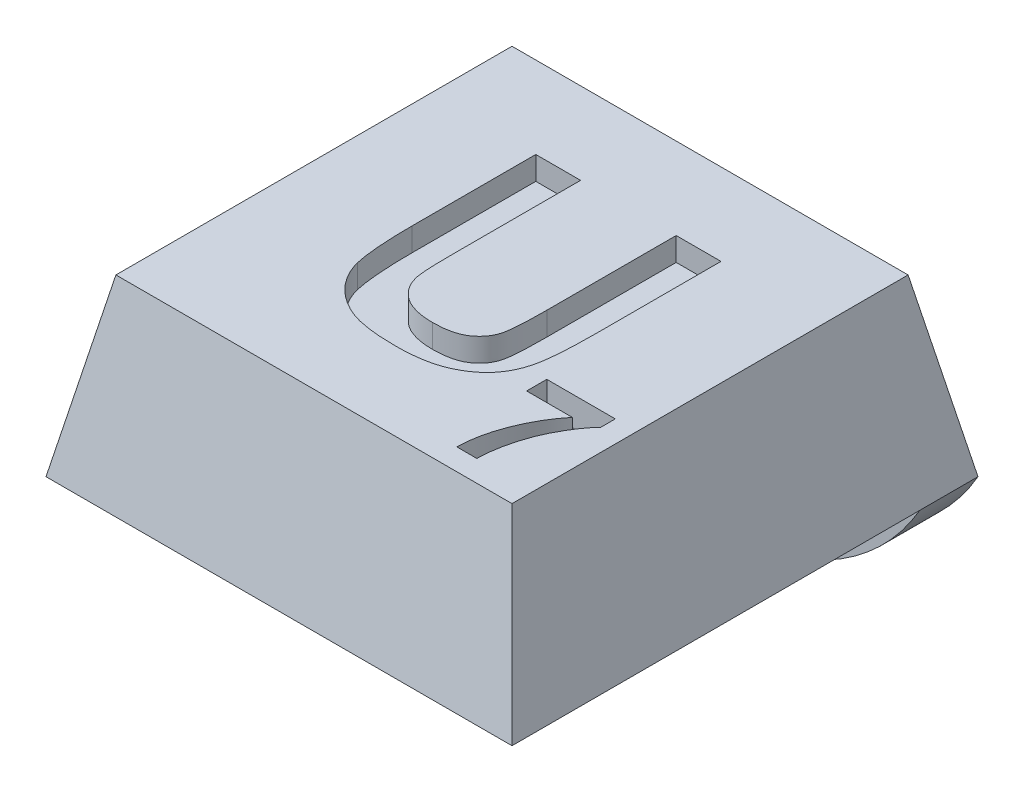
SolidWorks part; units mm, degrees
ref_plane "Front Plane" through (0, 0, 0) normal (0, 0, 1) x (1, 0, 0)
ref_plane "Top Plane" through (0, 0, 0) normal (0, 1, 0) x (1, 0, 0)
ref_plane "Right Plane" through (0, 0, 0) normal (1, 0, 0) x (0, 0, -1)
sketch "Sketch1" plane through (0, 0, 0) normal (0, 1, 0) x (1, 0, 0)
  line L1 (0, 0) -> (8, 0)
  line L2 (0, 0) -> (0, 8)
  line L3 (0, 8) -> (8, 8)
  line L4 (8, 0) -> (8, 8)
  dimension "D1" = 8
  dimension "D2" = 8
extrude "Boss-Extrude1" add sketch "Sketch1" along normal blind 3
sketch "Sketch2" plane through (0, 0, 0) normal (0, 0, 1) x (1, 0, 0)
  line L0 (0, 0) -> (0.6, 3)
  line L1 (0, 3) -> (8, 3) construction
  line L2 (0.6, 3) -> (0, 3)
  line L3 (0, 3) -> (0, 0)
  line L4 (8, 0) -> (7.4, 3)
  line L5 (7.4, 3) -> (8, 3)
  line L6 (8, 3) -> (8, 0)
  dimension "D1" = 0.6
  dimension "D2" = 0.6
extrude "Cut-Extrude1" cut sketch "Sketch2" against normal through all both and the other way through all
sketch "Sketch3" plane through (0, 0, 0) normal (1, 0, 0) x (0, 0, -1)
  line L0 (0, 0) -> (0.6, 3)
  line L1 (8, 3) -> (0, 3) construction
  line L2 (0.6, 3) -> (0, 3)
  line L3 (0, 3) -> (0, 0)
  line L4 (8, 3) -> (7.4, 3)
  line L5 (7.4, 3) -> (8, 0)
  line L6 (8, 3) -> (8, 0)
  dimension "D1" = 0.6
  dimension "D2" = 0.6
extrude "Cut-Extrude2" cut sketch "Sketch3" along normal blind 11
sketch "Sketch4" plane through (0, 0, 0) normal (0, -1, 0) x (1, 0, 0)
  line L0 (8, 0) -> (8, -8) construction
  line L3 (0, 0) -> (8, 0) construction
  circle A0 centre (4, -3.75) radius 1.75
  dimension "D1" = 3.5
  dimension "D2" = 4
  dimension "D3" = 3.75
extrude "Cut-Extrude3" cut sketch "Sketch4" against normal blind 0.4
sketch "Sketch5" plane through (0, 0, 0) normal (0, -1, 0) x (1, 0, 0)
  line L0 (8, 0) -> (8, -8) construction
  line L1 (0, -8) -> (8, -8)
  line L2 (0, -8) -> (0, -7)
  line L3 (0, -7) -> (8, -7)
  line L4 (8, -8) -> (8, -7)
  dimension "D1" = 1
extrude "Boss-Extrude2" add sketch "Sketch5" along normal blind 2
fillet "Fillet1" radius 4 2 edges at (8, -2, -7.5) (0, -2, -7.5)
sketch "Sketch6" plane through (0, 3, 0) normal (0, 1, 0) x (1, 0, 0)
  text T0 "U" font "Arial" height 4
extrude "Cut-Extrude4" cut sketch "Sketch6" against normal blind 0.4
sketch "Sketch7" plane through (0, 3, 0) normal (0, 1, 0) x (1, 0, 0)
  text T0 "7" font "Arial" height 1.8
extrude "Cut-Extrude5" cut sketch "Sketch7" against normal blind 0.5
